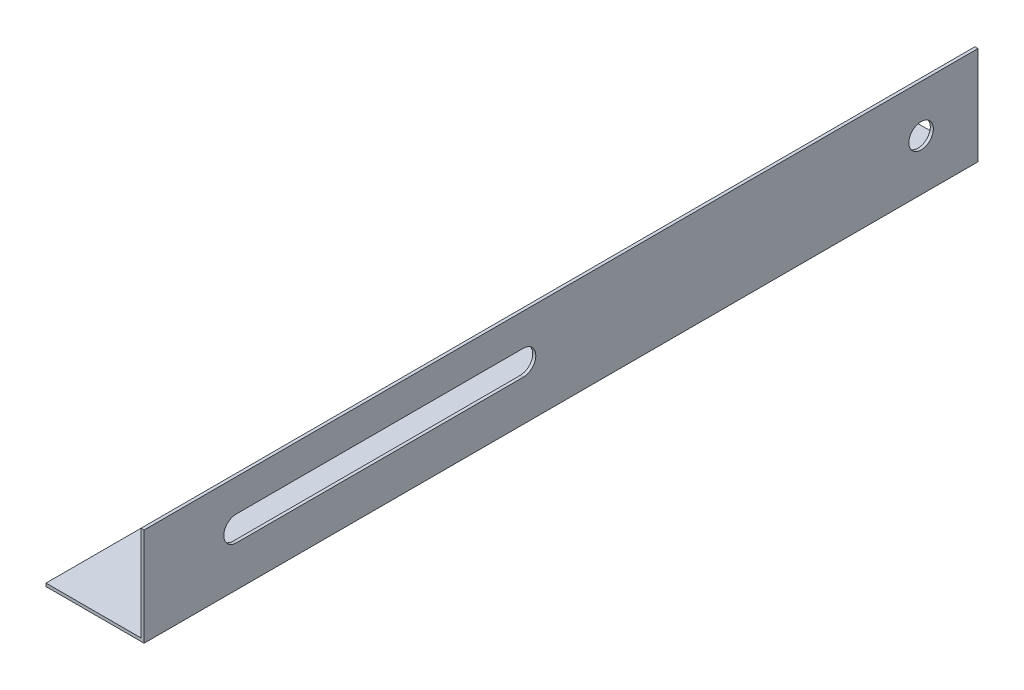
SolidWorks part; units mm, degrees
ref_plane "Front Plane" through (0, 0, 0) normal (0, 0, 1) x (1, 0, 0)
ref_plane "Top Plane" through (0, 0, 0) normal (0, 1, 0) x (1, 0, 0)
ref_plane "Right Plane" through (0, 0, 0) normal (1, 0, 0) x (0, 0, -1)
sketch "Sketch3" plane through (0, 0, 0) normal (0, 0, 1) x (1, 0, 0)
  line L18 (0, 0) -> (0, 1.5875)
  line L19 (0, 1.5875) -> (49.2125, 1.5875)
  line L20 (49.2125, 1.5875) -> (49.2125, 50.8)
  line L21 (49.2125, 50.8) -> (50.8, 50.8)
  line L22 (50.8, 50.8) -> (50.8, 0)
  line L23 (50.8, 0) -> (0, 0)
  dimension "D1" = 50.8
  dimension "D2" = 50.8
  dimension "D3" = 1.5875
  dimension "D4" = 1.5875
extrude "Boss-Extrude2" add sketch "Sketch3" along normal blind 431.8
sketch "Sketch8" plane through (50.8, 0, 0) normal (1, 0, 0) x (0, 0, -1)
  line L1 (-235.458, 27.6258) -> (-384.048, 27.6258) construction
  line L2 (-235.458, 21.1488) -> (-384.048, 21.1488)
  line L3 (-235.458, 34.1028) -> (-384.048, 34.1028)
  line L5 (0, 0) -> (0, 50.8) construction
  line L6 (-431.8, 0) -> (-431.8, 50.8) construction
  line L7 (-431.8, 50.8) -> (0, 50.8) construction
  arc A1 (-235.458, 21.1488) -> (-235.458, 34.1028) centre (-235.458, 27.6258) ccw
  arc A2 (-384.048, 34.1028) -> (-384.048, 21.1488) centre (-384.048, 27.6258) ccw
  circle A3 centre (-29.464, 26.416) radius 6.35
  point P6 (-309.753, 27.6258)
  dimension "D1" = 47.752
  dimension "D2" = 235.458
  dimension "D4" = 12.7
  dimension "D3" = 12.954
  dimension "D5" = 29.464
  dimension "D6" = 24.384
extrude "Cut-Extrude6" cut sketch "Sketch8" against normal blind 2.54
